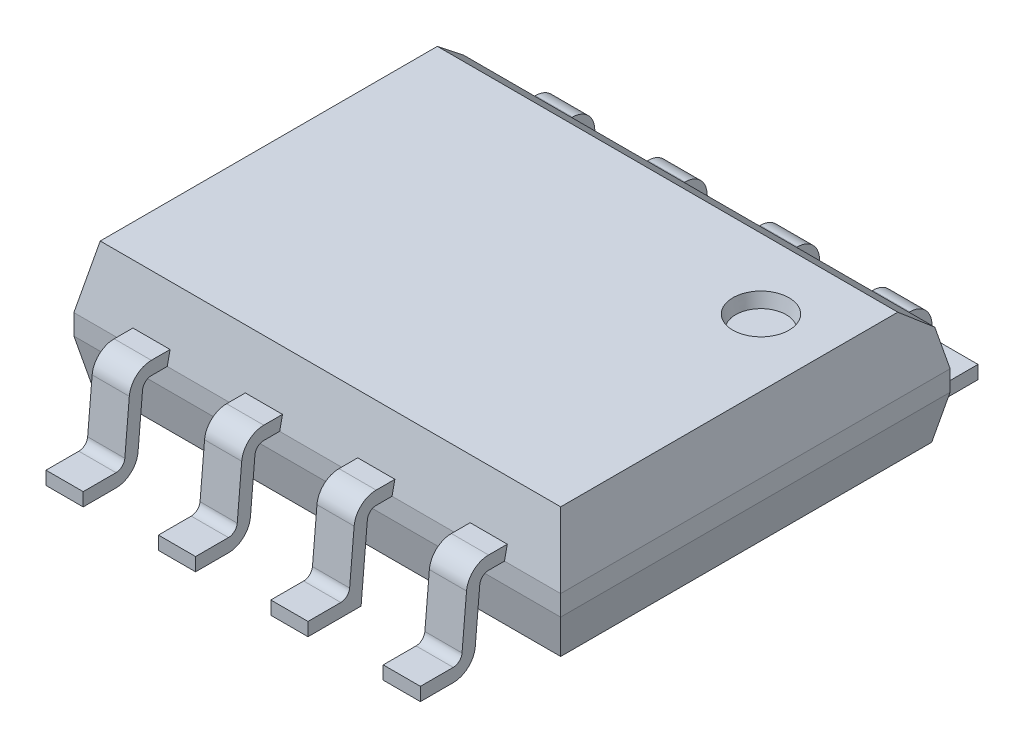
SolidWorks part; units mm, degrees
note: '?' marks a value the reader was unsure of.
ref_plane "Front Plane" through (0, 0, 0) normal (0, 0, 1) x (1, 0, 0)
ref_plane "Top Plane" through (0, 0, 0) normal (0, 1, 0) x (1, 0, 0)
ref_plane "Right Plane" through (0, 0, 0) normal (1, 0, 0) x (0, 0, -1)
ref_axis "Axis1" through (3.025, 0, 0) along (-1, 0, 0)?
sketch "Sketch1" plane through (0, 0, 0) normal (0, 1, 0) x (1, 0, 0)
  line L1 (-2.75, 2.2) -> (2.75, 2.2)
  line L2 (-2.75, 2.2) -> (-2.75, -2.2)
  line L3 (-2.75, -2.2) -> (2.75, -2.2)
  line L4 (2.75, 2.2) -> (2.75, -2.2)
  dimension "D1" = 5.5
  dimension "D2" = 4.4
  dimension "D3" = 2.75
  dimension "D4" = 2.2
extrude "Extrude1" add sketch "Sketch1" along normal blind 0.7 draft 12 and the other way blind 0.23
sketch "Sketch2" plane through (0, -0.23, 0) normal (0, -1, 0) x (1, 0, 0)
  line L4 (-2.75, 2.2) -> (-2.75, -2.2)
  line L5 (-2.75, -2.2) -> (2.75, -2.2)
  line L6 (2.75, -2.2) -> (2.75, 2.2)
  line L7 (2.75, 2.2) -> (-2.75, 2.2)
  line L8 (-2.75, 2.2) -> (-2.75, -2.2)
  line L9 (-2.75, -2.2) -> (2.75, -2.2)
  line L10 (2.75, -2.2) -> (2.75, 2.2)
  line L11 (2.75, 2.2) -> (-2.75, 2.2)
  dimension "D1" = 0
extrude "Extrude2" add sketch "Sketch2" along normal blind 0.49 draft 12
chamfer "Chamfer1" distance 0.3 angle 38.5 1 edges at (0, 0.7, -2.0512)
sketch "Sketch3" plane through (0, 0.7, 0) normal (0, 1, 0) x (-1, 0, 0)
  circle A0 centre (-1.8453, -0.9674) radius 0.3175
extrude "Cut-Extrude1" cut sketch "Sketch3" against normal blind 0.15 draft 12
sketch "Sketch4" plane through (0, 0, 0) normal (1, 0, 0) x (0, 0, -1)
  line L0 (0, 0.15) -> (0, 0)
  line L1 (-2.6874, -0.75) -> (-2.6087, 0.15)
  line L2 (-2.4713, 0) -> (2.4713, 0)
  line L3 (2.4713, 0) -> (2.55, -0.9)
  line L4 (-3.15, -0.75) -> (-2.6874, -0.75)
  line L5 (2.55, -0.9) -> (3.15, -0.9)
  line L6 (3.15, -0.9) -> (3.15, -0.75)
  line L7 (3.15, -0.75) -> (2.6874, -0.75)
  line L8 (2.6874, -0.75) -> (2.6087, 0.15)
  line L9 (2.6087, 0.15) -> (-2.6087, 0.15)
  line L10 (-3.15, -0.9) -> (-3.15, -0.75)
  line L11 (-2.55, -0.9) -> (-3.15, -0.9)
  line L12 (-2.4713, 0) -> (-2.55, -0.9)
  line L13 (2.2, 0) -> (-2.2, 0) construction
  line L14 (-2.0958, -0.72) -> (2.0958, -0.72) construction
  dimension "D1" = 0.15
  dimension "D2" = 0.15
  dimension "D3" = 0.15
  dimension "D4" = 0.6
  dimension "D5" = 6.3
  dimension "D6" = 95
  dimension "D7" = 0.18
extrude "Extrude3" add sketch "Sketch4" along normal blind 0.21 and the other way blind 0.21 from offset 0.635 contours L8 L9 L1 L4 L10 L11 L12 L2 L3 L5 L6 L7
pattern_linear "LPattern3" count 2 spacing 1.27 along (1, 0, 0) count 3 spacing 1.27 along (-1, 0, 0) of "Extrude3"
fillet "Fillet1" radius 0.1 16 edges at (1.905, -0.75, 2.6874) (0.635, -0.75, 2.6874) (-0.635, -0.75, 2.6874) (-1.905, -0.75, 2.6874) (1.905, 0, 2.4713) (0.635, 0, 2.4713) (-0.635, 0, 2.4713) (-1.905, 0, 2.4713) (1.905, -0.75, -2.6874) (0.635, -0.75, -2.6874) (-0.635, -0.75, -2.6874) (1.905, 0, -2.4713) (0.635, 0, -2.4713) (-0.635, 0, -2.4713) (-1.905, 0, -2.4713) (-1.905, -0.75, -2.6874)
fillet "Fillet2" radius 0.25 15 edges at (1.905, -0.9, 2.55) (1.905, 0.15, 2.6087) (-0.635, 0.15, 2.6087) (0.635, 0.15, 2.6087) (-0.635, -0.9, 2.55) (-1.905, -0.9, 2.55) (-1.905, 0.15, 2.6087) (1.905, 0.15, -2.6087) (0.635, 0.15, -2.6087) (-0.635, 0.15, -2.6087) (-1.905, 0.15, -2.6087) (1.905, -0.9, -2.55) (0.635, -0.9, -2.55) (-0.635, -0.9, -2.55) (-1.905, -0.9, -2.55)
ref_plane "Board Plane" through (0, -0.9, 0) normal (0, 1, 0) x (-1, 0, 0)
sketch "Component_Outline" plane through (0, -0.9, 0) normal (0, 1, 0) x (-1, 0, 0)
  line L0 (2.115, 3.15) -> (2.115, 2.2)
  line L1 (-1.695, -3.15) -> (-2.115, -3.15)
  line L2 (1.695, 3.15) -> (1.695, 2.2)
  line L3 (1.695, 2.2) -> (0.845, 2.2)
  line L4 (0.845, 3.15) -> (0.845, 2.2)
  line L5 (-0.425, -3.15) -> (-0.845, -3.15)
  line L6 (0.425, 3.15) -> (0.425, 2.2)
  line L7 (0.425, 2.2) -> (-0.425, 2.2)
  line L8 (-0.425, 3.15) -> (-0.425, 2.2)
  line L9 (0.845, -3.15) -> (0.425, -3.15)
  line L10 (-0.845, 3.15) -> (-0.845, 2.2)
  line L11 (-0.845, 2.2) -> (-1.695, 2.2)
  line L12 (-1.695, 3.15) -> (-1.695, 2.2)
  line L13 (1.695, -2.2) -> (0.845, -2.2)
  line L14 (1.695, -2.2) -> (1.695, -3.15)
  line L16 (0.845, -2.2) -> (0.845, -3.15)
  line L17 (0.425, -2.2) -> (-0.425, -2.2)
  line L18 (0.425, -2.2) -> (0.425, -3.15)
  line L20 (-0.425, -2.2) -> (-0.425, -3.15)
  line L21 (-0.845, -2.2) -> (-1.695, -2.2)
  line L22 (-0.845, -2.2) -> (-0.845, -3.15)
  line L24 (-1.695, -2.2) -> (-1.695, -3.15)
  line L25 (2.115, 2.2) -> (2.75, 2.2)
  line L26 (2.75, 2.2) -> (-2.75, 2.2) construction
  line L27 (2.75, 2.2) -> (2.75, -2.2)
  line L28 (2.75, -2.2) -> (2.115, -2.2)
  line L29 (2.115, -2.2) -> (2.115, -3.15)
  line L30 (2.115, -3.15) -> (1.695, -3.15)
  line L31 (-2.115, -3.15) -> (-2.115, -2.2)
  line L32 (-2.115, -2.2) -> (-2.75, -2.2)
  line L33 (-2.75, -2.2) -> (-2.75, 2.2)
  line L34 (-2.75, 2.2) -> (-2.115, 2.2)
  line L35 (-2.115, 2.2) -> (-2.115, 3.15)
  line L36 (-2.115, 3.15) -> (-1.695, 3.15)
  line L37 (1.695, 3.15) -> (2.115, 3.15)
  line L38 (0.425, 3.15) -> (0.845, 3.15)
  line L39 (-0.845, 3.15) -> (-0.425, 3.15)
  point P61 (0, 0)
